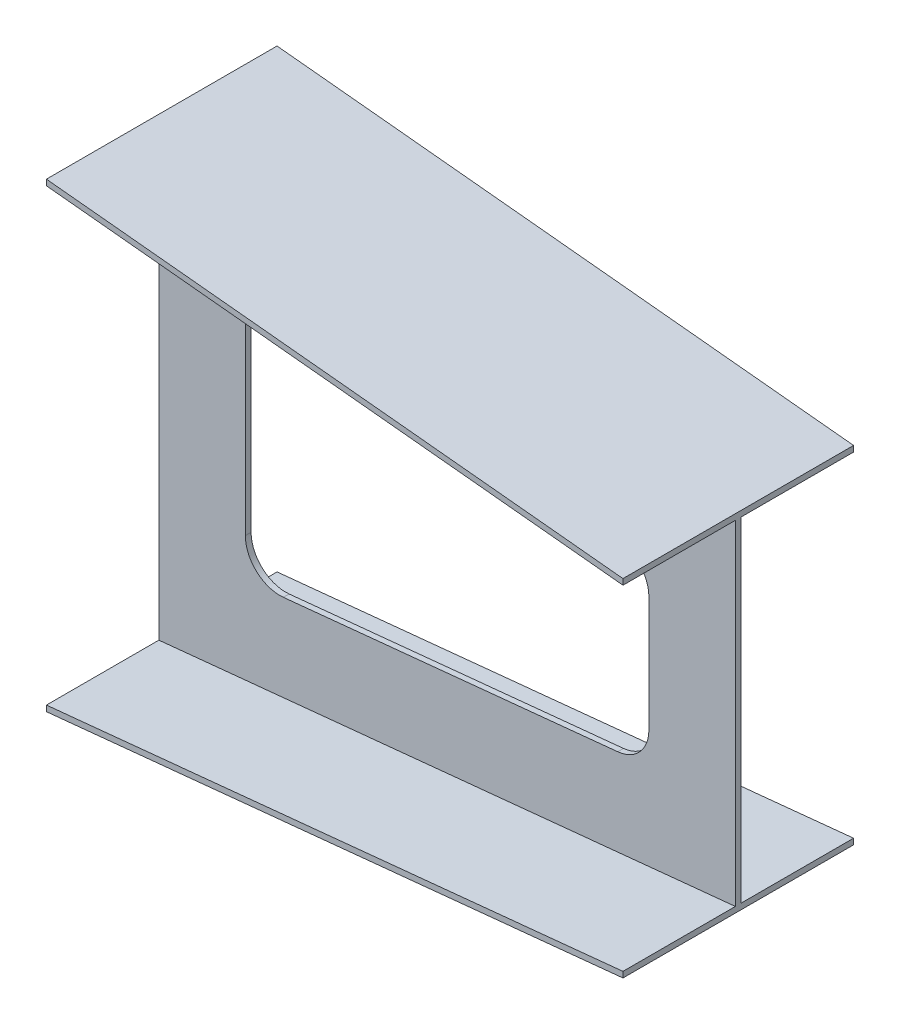
SolidWorks part; units mm, degrees
ref_plane "Front Plane" through (0, 0, 0) normal (0, 0, 1) x (1, 0, 0)
ref_plane "Top Plane" through (0, 0, 0) normal (0, 1, 0) x (1, 0, 0)
ref_plane "Right Plane" through (0, 0, 0) normal (1, 0, 0) x (0, 0, -1)
sketch "Sketch1" plane through (0, 0, 0) normal (1, 0, 0) x (0, 0, -1)
  line L1 (-205, 400) -> (195, 400)
  line L2 (-205, 400) -> (-205, 390)
  line L4 (195, 400) -> (195, 390)
  line L6 (-205, -390) -> (-205, -400)
  line L7 (-205, -400) -> (195, -400)
  line L8 (195, -390) -> (195, -400)
  line L15 (-205, -390) -> (-10, -390)
  line L16 (-5, 390) -> (-5, -590) construction
  line L18 (-205, 390) -> (-10, 390)
  line L19 (0, 0) -> (192.2403, 0) construction
  line L21 (-10, 390) -> (-10, -390)
  line L23 (0, 390) -> (0, -390)
  line L27 (0, 390) -> (195, 390)
  line L28 (0, -390) -> (195, -390)
  dimension "D1" = 400
  dimension "D2" = 10
  dimension "D3" = 800
  dimension "D4" = 10
ref_plane "Plane2" through (1000, 0, 0) normal (1, 0, 0) x (0, 0, -1)
sketch "Sketch4" plane through (1000, 0, -1000) normal (-1, 0, 0) x (0, 0, 1)
  line L1 (805, 300) -> (1205, 300)
  line L2 (805, 300) -> (805, 290)
  line L4 (1205, 300) -> (1205, 290)
  line L6 (805, -290) -> (805, -300)
  line L7 (805, -300) -> (1205, -300)
  line L8 (1205, -290) -> (1205, -300)
  line L15 (805, -290) -> (1000, -290)
  line L16 (1005, 390) -> (1005, -390) construction
  line L18 (805, 290) -> (1000, 290)
  line L19 (1010, -290) -> (1205, -290)
  line L21 (1000, 290) -> (1000, -290)
  line L23 (1010, 290) -> (1010, -290)
  line L24 (1010, 290) -> (1205, 290)
  line L26 (1010, 390) -> (1010, -390) construction
  line L27 (1000, 0) -> (820.2065, 0) construction
  dimension "D1" = 400
  dimension "D2" = 10
  dimension "D3" = 600
  dimension "D4" = 10
loft "Loft4" add profiles "Sketch1", "Sketch4" connector at (0, 390, 10) connector at (1000, 290, 10)
sketch "Sketch6" plane through (0, 0, 10) normal (0, 0, 1) x (1, 0, 0)
  line L8 (150, -224.2519) -> (850, -154.2519)
  line L9 (850, -154.2519) -> (850, 154.2519)
  line L10 (850, 154.2519) -> (150, 224.2519)
  line L11 (150, 224.2519) -> (150, -224.2519)
  line L12 (215.9702, -217.6548) -> (795.9702, -159.6548)
  line L13 (850, -99.9526) -> (850, 99.9526)
  line L14 (795.9702, 159.6548) -> (215.9702, 217.6548)
  line L15 (150, 157.9526) -> (150, -157.9526)
  arc A0 (150, -157.9526) -> (215.9702, -217.6548) centre (210, -157.9526) ccw
  arc A1 (850, 99.9526) -> (795.9702, 159.6548) centre (790, 99.9526) ccw
  arc A2 (850, -99.9526) -> (795.9702, -159.6548) centre (790, -99.9526) cw
  arc A3 (150, 157.9526) -> (215.9702, 217.6548) centre (210, 157.9526) cw
  dimension "D2" = 60
  dimension "D1" = 150
extrude "Cut-Extrude1" cut sketch "Sketch6" against normal blind 10
equation "\"ANS_h3\"=600"
equation "\"D3@Sketch4\"=\"ANS_h3\""
equation "\"ANS_w3\"=400"
equation "\"D1@Sketch4\"=\"ANS_w3\""
equation "\"ANS_h4\"=800"
equation "\"D3@Sketch1\"=\"ANS_h4\""
equation "\"ANS_w4\" = 400"
equation "\"D1@Sketch1\"=\"ANS_w4\""
